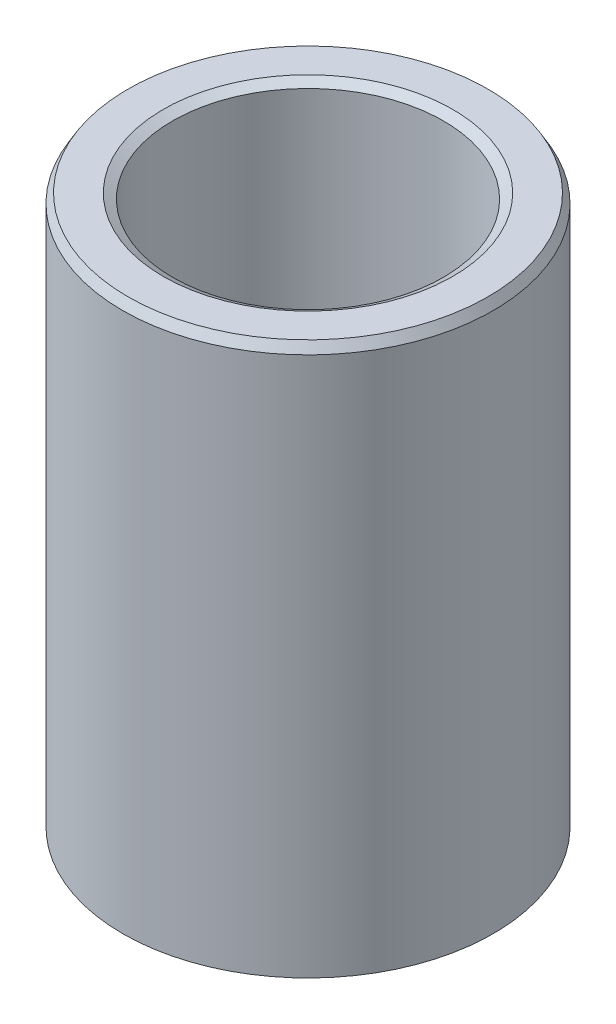
SolidWorks part; units mm, degrees
ref_plane "Front Plane" through (0, 0, 0) normal (0, 0, 1) x (1, 0, 0)
ref_plane "Top Plane" through (0, 0, 0) normal (0, 1, 0) x (1, 0, 0)
ref_plane "Right Plane" through (0, 0, 0) normal (1, 0, 0) x (0, 0, -1)
sketch "Sketch1" plane through (0, 0, 0) normal (0, 1, 0) x (1, 0, 0)
  circle A0 centre (0, 0) radius 35
  dimension "SLEEVE_OD" = 70
extrude "Boss-Extrude1" add sketch "Sketch1" along normal blind 104.6858
sketch "Sketch2" plane through (0, 0, 0) normal (0, 1, 0) x (1, 0, 0)
  circle A0 centre (0, 0) radius 25.5927
  dimension "BORE_D" = 51.1854
extrude "Cut-Extrude1" cut sketch "Sketch2" along normal through all
chamfer "Chamfer1" distance 1.7471 angle 30 4 edges at (0, 104.6858, 25.5927) (0, 0, 25.5927) (0, 0, 35) (0, 104.6858, 35) first distance on face at (0, 104.6858, 25.5927) first distance on face at (0, 0, 25.5927) first distance on face at (0, 104.6858, 35)
